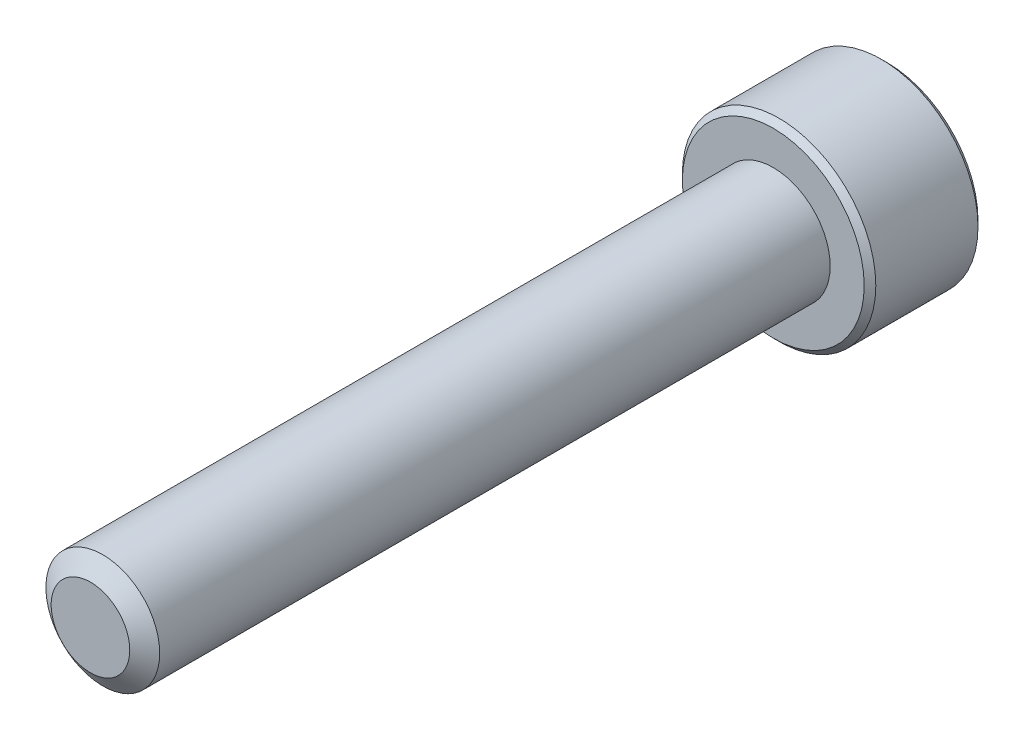
SolidWorks part; units mm, degrees
ref_plane "Front Plane" through (0, 0, 0) normal (0, 0, 1) x (1, 0, 0)
ref_plane "Top Plane" through (0, 0, 0) normal (0, 1, 0) x (1, 0, 0)
ref_plane "Right Plane" through (0, 0, 0) normal (1, 0, 0) x (0, 0, -1)
sketch "Sketch1" plane through (0, 0, 0) normal (0, 0, 1) x (1, 0, 0)
  circle A0 centre (0, 0) radius 2.5
  dimension "OD" = 5
extrude "Extrude1" add sketch "Sketch1" against normal blind 30
sketch "Sketch2" plane through (0, 0, 0) normal (0, 0, 1) x (1, 0, 0)
  circle A0 centre (0, 0) radius 2.5 construction
  circle A1 centre (0, 0) radius 2.5
curve "Helix/Spiral1" pitch 0.8 height 30.8 turns 38.5 parameters "pitch"=0.8
sketch "Sketch3" plane through (0, 0, 0) normal (1, 0, 0) x (0, 0, -1)
  line L0 (-0.7, 2.5) -> (-0.4, 1.9804)
  line L1 (-0.4, 1.9804) -> (-0.3, 1.9804)
  line L2 (-0.3, 1.9804) -> (0, 2.5)
  line L3 (-0.7, 2.5) -> (0, 2.5)
  line L4 (-0.35, 2.5) -> (-0.35, 1.9804) construction
  line L5 (-0.55, 2.2402) -> (-0.15, 2.2402) construction
  line L6 (0, 2.5) -> (0, -2.5) construction
  line L7 (0, -2.5) -> (30, -2.5) construction
  point P11 (3.6, -2.5)
  dimension "D1" = 0.1
  dimension "D2" = 0.4
  dimension "D3" = 60
  dimension "D4" = 3.6
sweep "Cut-Sweep1" [suppressed] cut profiles "Sketch3" path "Helix/Spiral1"
sketch "Sketch4" plane through (0, 0, 0) normal (1, 0, 0) x (0, 0, -1)
  line L0 (0.5417, 2.5) -> (0, 1.7264)
  line L1 (0, 1.7264) -> (0, 2.5)
  line L2 (0.5417, 2.5) -> (0, 2.5)
  line L3 (-0.7, 2.5) -> (0, 2.5) construction
  line L4 (0, 0) -> (7.0209, 0) construction
  dimension "D1" = 55
  dimension "D2" = 0.254
revolve "Cut-Revolve1" cut sketch "Sketch4" angle 360 about L4
sketch "Sketch5" [suppressed] plane through (0, 0, 0) normal (1, 0, 0) x (0, 0, -1)
  line L0 (30, -1.7838) -> (30, 1.991) construction
  line L1 (30, 2.5) -> (0.1203, 2.5)
  line L2 (30, 2.5) -> (30, 0)
  line L3 (30, 0) -> (0.0001, 0)
  line L4 (0.0001, 2.1698) -> (0.0001, 0)
  line L5 (0.1203, 2.5) -> (0.0001, 2.1698)
  line L6 (0, 0) -> (9.9695, 0) construction
  point P3 (0.0001, 2.5)
  point P10 (0.0001, 2.5)
  dimension "D1" = 0.3302
  dimension "Thread min" = 0.0001
  dimension "D3" = 20
revolve "partially thread" [suppressed] add sketch "Sketch5" angle 360 about L6
sketch "Sketch6" plane through (0, 0, -30) normal (0, 0, -1) x (-1, 0, 0)
  circle A0 centre (0, 0) radius 4.25
  dimension "head dia" = 8.5
extrude "Extrude2" add sketch "Sketch6" along normal blind 5
sketch "Sketch7" plane through (0, 0, -35) normal (0, 0, -1) x (-1, 0, 0)
  line L1 (0, 2.3094) -> (-2, 1.1547)
  line L2 (-2, 1.1547) -> (-2, -1.1547)
  line L3 (-2, -1.1547) -> (0, -2.3094)
  line L4 (0, -2.3094) -> (2, -1.1547)
  line L5 (2, -1.1547) -> (2, 1.1547)
  line L6 (2, 1.1547) -> (0, 2.3094)
  circle A0 centre (0, 0) radius 2 construction
  dimension "hex dia" = 4
extrude "Cut-Extrude1" cut sketch "Sketch7" against normal blind 3
sketch "Sketch8" plane through (0, 0, -35) normal (0, 0, -1) x (-1, 0, 0)
  circle A0 centre (0, 0) radius 2.3094
extrude "Cut-Extrude2" cut sketch "Sketch8" against normal through all draft 45
chamfer "Chamfer1" distance 0.255 angle 45 2 edges at (-4.25, 0, -35) (-4.25, 0, -30)
sketch "Sketch9" plane through (0, 0, 0) normal (1, 0, 0) x (0, 0, -1)
  line L0 (0, 2.5) -> (0, -2.5) construction
  line L1 (4.4, 2.5) -> (4.4, -2.5) construction
  dimension "D1" = 4.4
sketch "Sketch10" plane through (0, 0, 0) normal (1, 0, 0) x (0, 0, -1)
  line L0 (30, 2.5) -> (30, 0)
  line L1 (30, 2.5) -> (29.8, 2.5)
  line L2 (29.8, 2.5) -> (28.7645, 0)
  line L3 (30, 0) -> (28.7645, 0)
  line L4 (30, 3.995) -> (30, -3.995) construction
  dimension "D1" = 22.5
  dimension "D2" = 0.2
revolve "Revolve1" add sketch "Sketch10" angle 360 about L3
equation "\"D3@Helix/Spiral1\" = \"screw length@Extrude1\"+\"pitch@Helix/Spiral1\""
equation "\"D1@Sketch3\" = \"pitch@Helix/Spiral1\"*.125"
equation "\"D2@Sketch3\" = \"pitch@Helix/Spiral1\"*.5"
equation "\"D1@Cut-Extrude1\" = \"hex dia@Sketch7\"*.75"
equation "\"D1@Chamfer1\" = \"head dia@Sketch6\"*.03"
equation "\"D1@Sketch9\" = \"pitch@Helix/Spiral1\"*5.5"
equation "\"D2@Sketch10\" = \"pitch@Helix/Spiral1\"*.25"
equation "\"D4@Sketch3\" = \"pitch@Helix/Spiral1\"*4.50"
